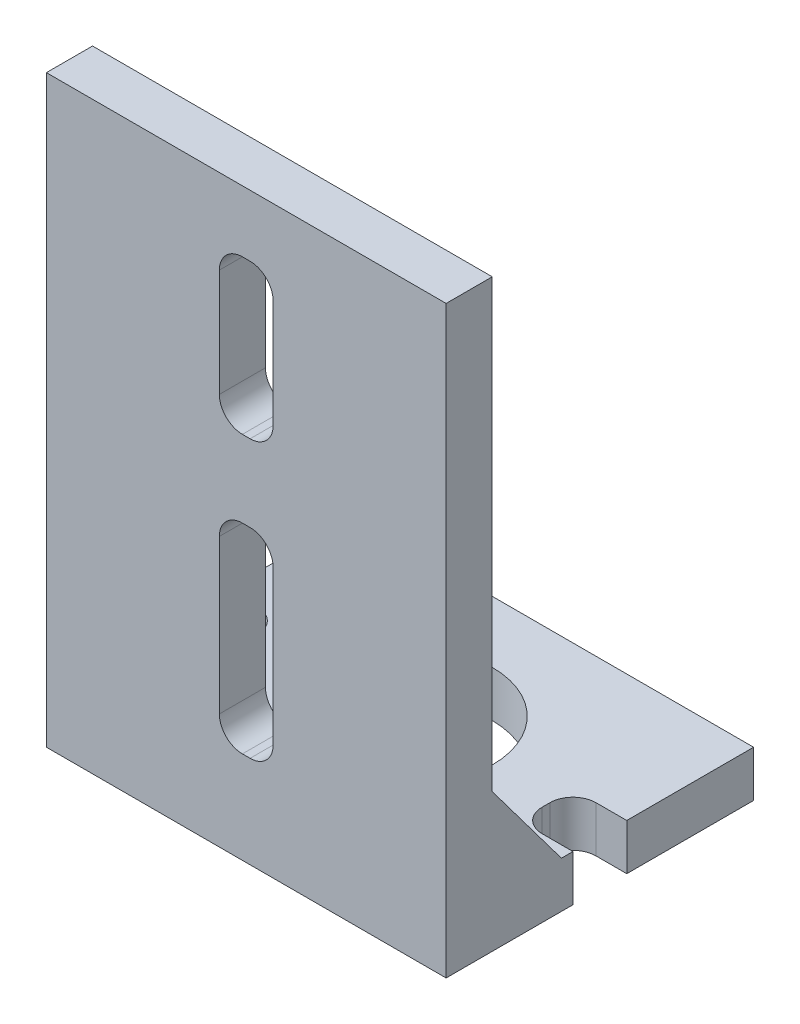
SolidWorks part; units mm, degrees
ref_plane "Front" through (0, 0, 0) normal (0, 0, 1) x (1, 0, 0)
ref_plane "Top" through (0, 0, 0) normal (0, 1, 0) x (1, 0, 0)
ref_plane "Right" through (0, 0, 0) normal (1, 0, 0) x (0, 0, -1)
sketch "Esboço1" plane through (0, 0, 0) normal (0, 1, 0) x (1, 0, 0)
  line L1 (-4.922, 9.0418) -> (21.078, 9.0418)
  line L2 (-4.922, 9.0418) -> (-4.922, -10.9582)
  line L3 (-4.922, -10.9582) -> (21.078, -10.9582)
  line L4 (21.078, 9.0418) -> (21.078, -10.9582)
  dimension "D1" = 26
  dimension "D2" = 20
extrude "Ressalto-extrusão1" add sketch "Esboço1" along normal blind 3
sketch "Esboço2" plane through (0, 3, 0) normal (0, 1, 0) x (1, 0, 0)
  line L0 (-4.922, 9.0418) -> (-4.922, -10.9582) construction
  line L1 (21.078, -10.9582) -> (-4.922, -10.9582)
  line L2 (21.078, -10.9582) -> (21.078, -7.9582)
  line L3 (21.078, -7.9582) -> (-4.922, -7.9582)
  line L4 (-4.922, -10.9582) -> (-4.922, -7.9582)
  dimension "D1" = 3
extrude "Ressalto-extrusão2" add sketch "Esboço2" along normal blind 35
sketch "Esboço3" plane through (0, 3, 0) normal (0, 1, 0) x (1, 0, 0)
  line L0 (21.078, -7.9582) -> (21.078, -3.4582)
  line L1 (-4.922, -7.9582) -> (-1.922, -7.9582)
  line L2 (-4.922, -7.9582) -> (-4.922, -3.4582)
  line L3 (-4.922, -3.4582) -> (-1.922, -3.4582)
  line L4 (-1.922, -7.9582) -> (-1.922, -3.4582)
  line L5 (18.078, -3.4582) -> (21.078, -3.4582)
  line L6 (18.078, -7.9582) -> (18.078, -3.4582)
  line L7 (18.078, -7.9582) -> (21.078, -7.9582)
  dimension "D1" = 3
  dimension "D2" = 4.5
  dimension "D3" = 2
extrude "Ressalto-extrusão3" add sketch "Esboço3" along normal blind 6
sketch "Esboço4" plane through (-4.922, 0, 0) normal (-1, 0, 0) x (0, 0, 1)
  line L0 (3.4582, 3) -> (7.9582, 9)
  line L1 (7.9582, 9) -> (3.4582, 9)
  line L2 (3.4582, 9) -> (3.4582, 3)
extrude "Corte-extrusão1" cut sketch "Esboço4" against normal through all
sketch "Esboço5" plane through (0, 0, 10.9582) normal (0, 0, 1) x (1, 0, 0)
  line L0 (8.078, 0) -> (8.078, 6) construction
  line L1 (-4.922, 0) -> (21.078, 0) construction
  line L2 (-4.922, 38) -> (21.078, 38) construction
  line L3 (8.078, 38) -> (8.078, 34)
  line L4 (8.078, 19) -> (8.078, 24)
  line L5 (8.078, 0) -> (8.078, 6)
  line L6 (8.078, 19) -> (8.078, 24) construction
  line L8 (6.328, 34) -> (9.828, 34)
  line L9 (6.328, 24) -> (9.828, 24)
  line L10 (9.828, 24) -> (9.828, 34)
  line L11 (6.328, 34) -> (6.328, 24)
  line L12 (6.328, 19) -> (9.828, 19)
  line L13 (9.828, 19) -> (9.828, 6)
  line L14 (9.828, 6) -> (6.328, 6)
  line L15 (6.328, 6) -> (6.328, 19)
  line L16 (8.078, 34) -> (8.078, 38) construction
  point P10 (8.078, 21.5)
  point P14 (8.078, 34)
  point P17 (8.078, 24)
  point P20 (8.078, 19)
  dimension "D1" = 4
  dimension "D2" = 5
  dimension "D3" = 6
  dimension "D5" = 13
extrude "Corte-extrusão2" cut sketch "Esboço5" against normal up to next contours L8 L11 L9 L10 | L15 L14 L13 L12 region at (8.078, 29, 10.9582) region at (8.078, 12.5, 10.9582)
fillet "Filete2" radius 1.5 6 edges at (9.828, 34, 9.4582) (6.328, 34, 9.4582) (9.828, 24, 9.4582) (6.328, 24, 9.4582) (9.828, 19, 9.4582) (6.328, 19, 9.4582)
fillet "Filete3" radius 1.5 1 edges at (6.328, 6, 9.4582)
fillet "Filete4" radius 1.5 1 edges at (9.828, 6, 9.4582)
sketch "Esboço6" plane through (0, 0, 0) normal (0, -1, 0) x (1, 0, 0)
  line L0 (-4.922, -9.0418) -> (-4.922, 10.9582) construction
  line L1 (-8.422, 2.7082) -> (-1.422, 2.7082)
  line L2 (-8.422, 2.7082) -> (-8.422, -0.7918)
  line L3 (-8.422, -0.7918) -> (-1.422, -0.7918)
  line L4 (-1.422, 2.7082) -> (-1.422, -0.7918)
  line L5 (-8.422, 2.7082) -> (-1.422, -0.7918) construction
  line L6 (-8.422, -0.7918) -> (-1.422, 2.7082) construction
  line L7 (21.078, 10.9582) -> (21.078, -9.0418) construction
  line L8 (24.578, -0.7918) -> (17.578, -0.7918)
  line L9 (24.578, -0.7918) -> (24.578, 2.7082)
  line L10 (24.578, 2.7082) -> (17.578, 2.7082)
  line L11 (17.578, -0.7918) -> (17.578, 2.7082)
  line L12 (24.578, -0.7918) -> (17.578, 2.7082) construction
  line L13 (24.578, 2.7082) -> (17.578, -0.7918) construction
  point P0 (-4.922, 0.9582)
  point P7 (21.078, 0.9582)
  dimension "D1" = 7
  dimension "D2" = 3.5
  dimension "D3" = 7
  dimension "D4" = 3.5
extrude "Corte-extrusão3" cut sketch "Esboço6" against normal up to next
fillet "Filete5" radius 1.5 4 edges at (17.578, 1.5, -0.7918) (17.578, 1.5, 2.7082) (-1.422, 1.5, -0.7918) (-1.422, 1.5, 2.7082)
sketch "Esboço7" plane through (0, 0, 0) normal (0, -1, 0) x (1, 0, 0)
  line L0 (8.078, 10.9582) -> (8.078, -9.0418) construction
  line L1 (-4.922, 10.9582) -> (21.078, 10.9582) construction
  line L2 (21.078, -9.0418) -> (-4.922, -9.0418) construction
  line L3 (8.078, 10.9582) -> (8.078, 7.9582) construction
  line L4 (8.078, 7.9582) -> (8.078, -7.0418)
  circle A0 centre (8.078, 0.4582) radius 5.5
  dimension "D2" = 15
  dimension "D1" = 3
extrude "Corte-extrusão4" cut sketch "Esboço7" against normal up to next contours L4 A0 | L4 A0 region at (10.4123, 0, 0.4582) region at (5.7437, 0, 0.4582)
